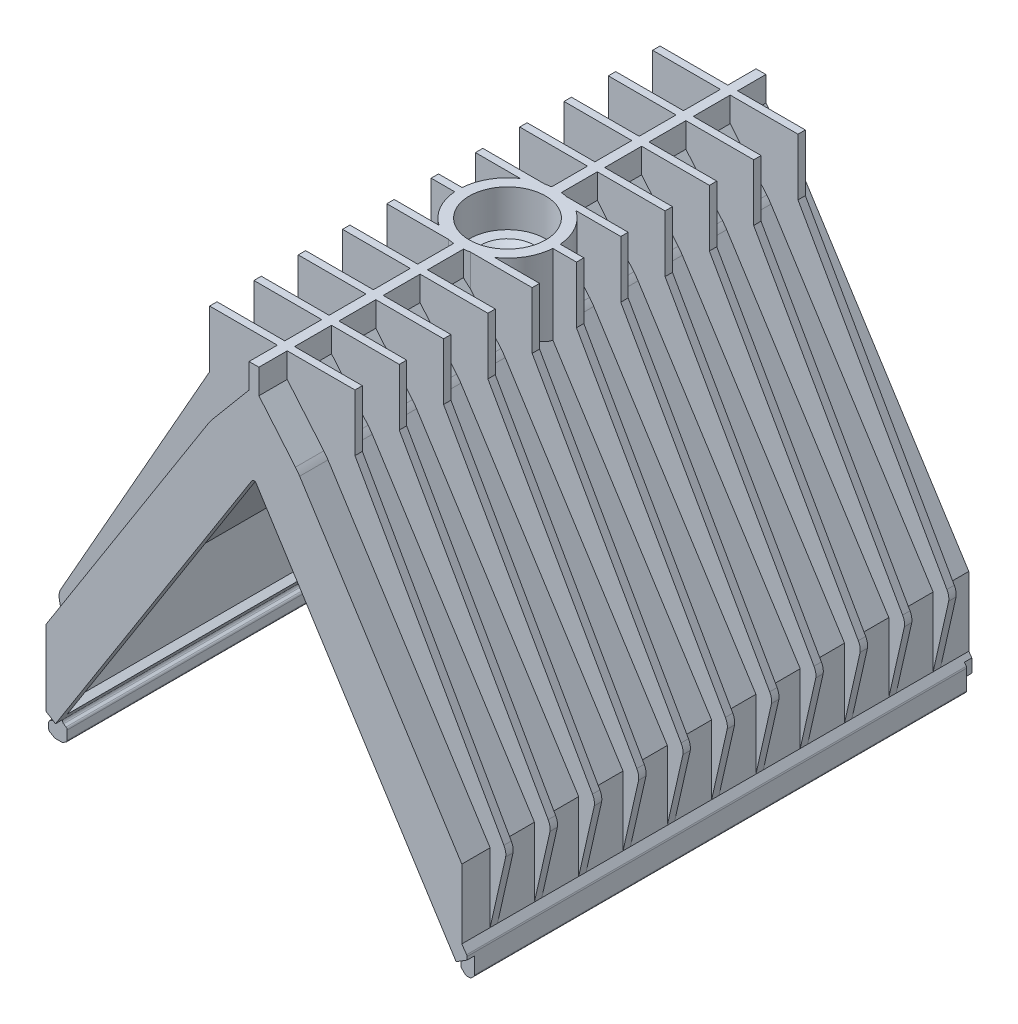
SolidWorks part; units mm, degrees
ref_plane "Front Plane" through (0, 0, 0) normal (0, 0, 1) x (1, 0, 0)
ref_plane "Top Plane" through (0, 0, 0) normal (0, 1, 0) x (1, 0, 0)
ref_plane "Right Plane" through (0, 0, 0) normal (1, 0, 0) x (0, 0, -1)
sketch "Sketch1" plane through (0, 0, 0) normal (0, 0, 1) x (1, 0, 0)
  line L0 (0, 0) -> (0, 124.0259) construction
  line L5 (-78.9086, 0) -> (78.9086, 0) construction
  line L9 (-0.8437, 122.6998) -> (-78.9086, 0) construction
  line L10 (0.8437, 122.6998) -> (81.0558, -3.3749) construction
  line L11 (81.0558, -3.3749) -> (83.5869, -1.7645) construction
  line L12 (83.5869, -1.7645) -> (3.3749, 124.3102) construction
  line L13 (-3.3749, 124.3102) -> (-81.4398, 1.6104) construction
  line L14 (-81.4398, 1.6104) -> (-78.9086, 0) construction
  line L15 (-81.4398, 1.6104) -> (-81.4398, 29.5541)
  line L16 (-81.4398, 29.5541) -> (-16.0306, 132.3621)
  line L17 (78.9086, 0) -> (81.4398, 1.6104) construction
  line L18 (81.4398, 1.6104) -> (81.4398, 29.5541)
  line L19 (81.4398, 29.5541) -> (16.0306, 132.3621)
  line L20 (-81.4398, 1.6104) -> (-78.9086, 0)
  line L23 (-84.4398, -4.2849) -> (-84.4398, 30.4275)
  line L24 (-84.4398, 30.4275) -> (-18.5617, 133.9725)
  line L25 (81.0558, -3.3749) -> (83.5869, -1.7645)
  line L26 (83.5869, -1.7645) -> (81.4398, 1.6104)
  line L29 (86.5869, -8.9852) -> (86.5869, -1.0301)
  line L30 (86.4044, -0.4541) -> (84.4398, 2.3339)
  line L31 (84.4398, 2.3339) -> (84.4398, 30.4275)
  line L32 (84.4398, 30.4275) -> (18.5617, 133.9725)
  line L33 (-106.5938, 164) -> (109.6618, 164) construction
  line L34 (0, 122.163) -> (0, 164) construction
  line L35 (0, 156.3889) -> (-16.853, 136.3043)
  line L36 (0, 156.3889) -> (16.853, 136.3043)
  line L37 (-78.9086, -5.5791) -> (-78.9086, -9.1985)
  line L38 (-81.1766, -10.9306) -> (-83.6407, -10.9306)
  line L39 (-78.9086, 0) -> (-80.65, -2.737)
  line L42 (-84.4398, -4.8622) -> (-84.4398, 3.8538) construction
  line L45 (-84.1407, -10.7966) -> (-85.9086, -9.7759)
  line L46 (-80.343, -4.1175) -> (-79.3718, -4.7354)
  line L49 (81.0558, -3.3749) -> (82.1294, -5.0623)
  line L50 (81.8225, -6.4428) -> (81.519, -6.6359)
  line L51 (81.0558, -7.4796) -> (81.0558, -8.5163)
  line L52 (81.3487, -9.2235) -> (82.7629, -10.6377)
  line L53 (83.47, -10.9306) -> (84.6416, -10.9306)
  line L54 (85.3487, -10.6377) -> (86.294, -9.6923)
  line L55 (-86.4086, -8.9098) -> (-86.4086, -6.5763)
  line L56 (-79.4086, -10.0645) -> (-80.6766, -10.7966)
  line L57 (-85.9086, -5.7102) -> (-84.9398, -5.1509)
  arc A0 (3.3749, 124.3102) -> (-3.3749, 124.3102) centre (0, 122.163) ccw construction
  arc A1 (0.8437, 122.6998) -> (-0.8437, 122.6998) centre (0, 122.163) ccw construction
  arc A2 (16.0306, 132.3621) -> (-16.0306, 132.3621) centre (0, 122.163) ccw
  arc A3 (-18.5617, 133.9725) -> (-16.853, 136.3043) centre (0, 122.163) cw
  arc A6 (16.853, 136.3043) -> (18.5617, 133.9725) centre (0, 122.163) cw
  arc A7 (-80.65, -2.737) -> (-80.343, -4.1175) centre (-79.8062, -3.2738) ccw
  arc A8 (-78.9086, -5.5791) -> (-79.3718, -4.7354) centre (-79.9086, -5.5791) ccw
  arc A9 (-79.4086, -10.0645) -> (-78.9086, -9.1985) centre (-79.9086, -9.1985) ccw
  arc A10 (-81.1766, -10.9306) -> (-80.6766, -10.7966) centre (-81.1766, -9.9306) ccw
  arc A11 (-83.6407, -10.9306) -> (-84.1407, -10.7966) centre (-83.6407, -9.9306) cw
  arc A12 (-85.9086, -9.7759) -> (-86.4086, -8.9098) centre (-85.4086, -8.9098) cw
  arc A13 (-85.9086, -5.7102) -> (-86.4086, -6.5763) centre (-85.4086, -6.5763) ccw
  arc A14 (-84.4398, -4.2849) -> (-84.9398, -5.1509) centre (-85.4398, -4.2849) cw
  arc A15 (86.5869, -1.0301) -> (86.4044, -0.4541) centre (85.5869, -1.0301) ccw
  arc A16 (86.294, -9.6923) -> (86.5869, -8.9852) centre (85.5869, -8.9852) ccw
  arc A17 (84.6416, -10.9306) -> (85.3487, -10.6377) centre (84.6416, -9.9306) ccw
  arc A18 (83.47, -10.9306) -> (82.7629, -10.6377) centre (83.47, -9.9306) cw
  arc A19 (81.3487, -9.2235) -> (81.0558, -8.5163) centre (82.0558, -8.5163) cw
  arc A20 (81.519, -6.6359) -> (81.0558, -7.4796) centre (82.0558, -7.4796) ccw
  arc A21 (81.8225, -6.4428) -> (82.1294, -5.0623) centre (81.2857, -5.5991) ccw
  point P30 (85.4221, 0.9399)
  point P67 (-80.9086, -10.9306)
  point P70 (-83.9086, -10.9306)
  point P85 (85.0558, -10.9306)
  point P88 (83.0558, -10.9306)
  point P91 (81.0558, -8.9306)
  point P94 (81.0558, -6.9306)
  point P97 (82.6662, -5.906)
  point P99 (-85.4242, -5.4306)
  point P100 (-79.8574, -4.4265)
  dimension "D4" = 151
  dimension "D5" = 160
  dimension "D6" = 4
  dimension "D7" = 1
  dimension "D10" = 19
  dimension "D18" = 120
  dimension "D29" = 1
  dimension "D30" = 1
  dimension "D32" = 1
  dimension "D1" = 3
  dimension "D2" = 3
  dimension "D3" = 147
  dimension "D8" = 15
  dimension "D9" = 15
  dimension "D11" = 3
  dimension "D12" = 3
  dimension "D13" = 135
  dimension "D14" = 3
  dimension "D15" = 3
  dimension "D16" = 3
  dimension "D17" = 3
  dimension "D19" = 140
  dimension "D20" = 120
  dimension "D21" = 3
  dimension "D22" = 2
  dimension "D23" = 135
  dimension "D24" = 2
  dimension "D25" = 2
  dimension "D26" = 3
  dimension "D27" = 2
  dimension "D28" = 150
  dimension "D31" = 7.5
  dimension "D33" = 5.5
  dimension "D34" = 6.5041
extrude "Boss-Extrude1" add sketch "Sketch1" along normal blind 100 and the other way blind 100
sketch3d "3DSketch3" plane through (0, 0, 0) normal (0, 0, 1) x (1, 0, 0)
  dimension "D1" = 175
sketch "Sketch2" plane through (0, 164.0694, 0) normal (0, -1, 0) x (-1, 0, 0)
  line L0 (16.0306, 100) -> (-16.0306, 100) construction
  line L1 (96, -1.5) -> (-96, -1.5)
  line L2 (96, -1.5) -> (96, 1.5)
  line L3 (96, 1.5) -> (-96, 1.5)
  line L4 (-96, -1.5) -> (-96, 1.5)
  line L5 (96, -1.5) -> (-96, 1.5) construction
  line L6 (96, 1.5) -> (-96, -1.5) construction
  line L7 (0, 0) -> (0, 114.6927) construction
  line L9 (0, 0) -> (96, 0) construction
  line L10 (-96, -19.5) -> (96, -19.5)
  line L11 (-96, -19.5) -> (-96, -16.5)
  line L12 (-96, -16.5) -> (96, -16.5)
  line L13 (96, -19.5) -> (96, -16.5)
  line L14 (-96, -19.5) -> (96, -16.5) construction
  line L15 (-96, -16.5) -> (96, -19.5) construction
  line L16 (-96, -37.5) -> (96, -37.5)
  line L17 (-96, -37.5) -> (-96, -34.5)
  line L18 (-96, -34.5) -> (96, -34.5)
  line L19 (96, -37.5) -> (96, -34.5)
  line L20 (-96, -37.5) -> (96, -34.5) construction
  line L21 (-96, -34.5) -> (96, -37.5) construction
  line L22 (-96, -55.5) -> (96, -55.5)
  line L23 (-96, -55.5) -> (-96, -52.5)
  line L24 (-96, -52.5) -> (96, -52.5)
  line L25 (96, -55.5) -> (96, -52.5)
  line L26 (-96, -55.5) -> (96, -52.5) construction
  line L27 (-96, -52.5) -> (96, -55.5) construction
  line L28 (-96, -73.5) -> (96, -73.5)
  line L29 (-96, -73.5) -> (-96, -70.5)
  line L30 (-96, -70.5) -> (96, -70.5)
  line L31 (96, -73.5) -> (96, -70.5)
  line L32 (-96, -73.5) -> (96, -70.5) construction
  line L33 (-96, -70.5) -> (96, -73.5) construction
  line L34 (-96, -91.5) -> (96, -91.5)
  line L35 (-96, -91.5) -> (-96, -88.5)
  line L36 (-96, -88.5) -> (96, -88.5)
  line L37 (96, -91.5) -> (96, -88.5)
  line L38 (-96, -91.5) -> (96, -88.5) construction
  line L39 (-96, -88.5) -> (96, -91.5) construction
  line L40 (-96, 88.5) -> (96, 91.5) construction
  line L41 (-96, 91.5) -> (96, 88.5) construction
  line L42 (-96, 70.5) -> (96, 73.5) construction
  line L43 (-96, 73.5) -> (96, 70.5) construction
  line L44 (-96, 52.5) -> (96, 55.5) construction
  line L45 (-96, 55.5) -> (96, 52.5) construction
  line L46 (-96, 34.5) -> (96, 37.5) construction
  line L47 (-96, 37.5) -> (96, 34.5) construction
  line L48 (-96, 16.5) -> (96, 19.5) construction
  line L49 (-96, 19.5) -> (96, 16.5) construction
  line L50 (96, 91.5) -> (96, 88.5)
  line L51 (-96, 88.5) -> (96, 88.5)
  line L52 (-96, 91.5) -> (-96, 88.5)
  line L53 (-96, 91.5) -> (96, 91.5)
  line L54 (96, 73.5) -> (96, 70.5)
  line L55 (-96, 70.5) -> (96, 70.5)
  line L56 (-96, 73.5) -> (-96, 70.5)
  line L57 (-96, 73.5) -> (96, 73.5)
  line L58 (96, 55.5) -> (96, 52.5)
  line L59 (-96, 52.5) -> (96, 52.5)
  line L60 (-96, 55.5) -> (-96, 52.5)
  line L61 (-96, 55.5) -> (96, 55.5)
  line L62 (96, 37.5) -> (96, 34.5)
  line L63 (-96, 34.5) -> (96, 34.5)
  line L64 (-96, 37.5) -> (-96, 34.5)
  line L65 (-96, 37.5) -> (96, 37.5)
  line L66 (96, 19.5) -> (96, 16.5)
  line L67 (-96, 16.5) -> (96, 16.5)
  line L68 (-96, 19.5) -> (-96, 16.5)
  line L69 (-96, 19.5) -> (96, 19.5)
  line L70 (-2, -100) -> (2, -100)
  line L71 (-2, -100) -> (-2, 100)
  line L72 (-2, 100) -> (2, 100)
  line L73 (2, -100) -> (2, 100)
  line L74 (-2, -100) -> (2, 100) construction
  line L75 (-2, 100) -> (2, -100) construction
  circle A0 centre (0, 0) radius 20
  point P0 (0, 0)
  point P10 (0, -18)
  point P15 (0, -36)
  point P20 (0, -54)
  point P25 (0, -72)
  point P30 (0, -90)
  point P56 (0, 90)
  point P57 (0, 72)
  point P58 (0, 54)
  point P59 (0, 36)
  point P60 (0, 18)
  dimension "D9" = 40
  dimension "D1" = 96
  dimension "D2" = 3
  dimension "D3" = 15
  dimension "D4" = 15
  dimension "D5" = 15
  dimension "D6" = 15
  dimension "D7" = 15
  dimension "D8" = 4
extrude "Boss-Extrude3" add sketch "Sketch2" along direction (0, -1, 0) on the side of the normal blind 175 contours L73 L51 L50 L53 | L51 L73 L53 L71 | L53 L73 L72 L71 | L51 L71 L53 L52 | L57 L73 L51 L71 | L55 L73 L57 L71 | L73 L55 L54 L57 | L55 L71 L57 L56 | L73 L59 L58 L61 | L65 L73 L59 L71 | L59 L71 L61 L60 | L59 L73 L61 L71 | L61 L73 L55 L71 | L73 L63 L62 L65 | L63 L73 L65 L71 | L63 L71 L65 L64 | A0 L73 L63 L71 | L69 A0 L67 L71 | L67 A0 L69 L73 | A0 L67 L66 L69 | L69 A0 L73 | L73 A0 L71 L69 | L71 A0 L69 | L67 A0 L3 L71 | L3 L73 L67 L71 | L3 A0 L67 L73 | L71 A0 L73 L10 | L73 A0 L10 | L1 A0 L12 L71 | L12 A0 L10 L71 | L10 A0 L71 | L10 L73 L12 L71 | L10 A0 L12 L73 | L12 A0 L1 L73 | L12 L73 L1 L71 | L1 A0 L3 L73 | L1 L73 L3 L71 | L3 A0 L1 L71 | A0 L3 L4 L1 | A0 L1 L2 L3 | A0 L69 L68 L67 | A0 L10 L13 L12 | A0 L12 L11 L10 | L73 L16 L19 L18 | L16 L71 L18 L17 | L73 L34 L37 L36 | L73 L28 L31 L30 | L73 L22 L25 L24 | L34 L71 L36 L35 | L70 L73 L34 L71 | L34 L73 L36 L71 | L36 L73 L28 L71 | L30 L73 L22 L71 | L28 L73 L30 L71 | L28 L71 L30 L29 | L22 L71 L24 L23 | L22 L73 L24 L71 | L24 L73 L16 L71 | L16 L73 L18 L71 | A0 L71 L18 L73 | L53 L50 L51 L52 | L73 L72 L71 L70 region at (-57.9906, 164.0694, 0) region at (-9.7744, 164.0694, 8.3272) region at (-10.9906, 164.0694, 0) region at (0, 164.0694, 9) region at (0, 164.0694, 0) region at (-5.5128, 164.0694, 17.7465) region at (-52.2103, 164.0694, 18.0187) region at (-9.7744, 164.0694, -8.3272) region at (9.7744, 164.0694, 8.3272) region at (10.9906, 164.0694, 0) region at (0, 164.0694, 18) region at (0, 164.0694, -9) region at (-2.8618, 164.0694, 19.6426) region at (-52.2103, 164.0694, -18.0187) region at (-5.5128, 164.0694, -17.7465) region at (57.9906, 164.0694, 0) region at (5.5128, 164.0694, 17.7465) region at (9.7744, 164.0694, -8.3272) region at (0, 164.0694, 19.7343) region at (0, 164.0694, 27.2333) region at (-2.8618, 164.0694, -19.6426) region at (52.2103, 164.0694, 18.0187) region at (2.8618, 164.0694, 19.6426) region at (5.5128, 164.0694, -17.7465) region at (0, 164.0694, -19.7343) region at (0, 164.0694, 36) region at (-49, 164.0694, 36) region at (0, 164.0694, -27.2333) region at (52.2103, 164.0694, -18.0187) region at (2.8618, 164.0694, -19.6426) region at (49, 164.0694, 36) region at (0, 164.0694, 45) region at (-49, 164.0694, -36) region at (0, 164.0694, -36) region at (0, 164.0694, 54) region at (-49, 164.0694, 54) region at (49, 164.0694, -36) region at (0, 164.0694, -45) region at (49, 164.0694, 54) region at (0, 164.0694, 63) region at (-49, 164.0694, -54) region at (0, 164.0694, -54) region at (0, 164.0694, 72) region at (-49, 164.0694, 72) region at (49, 164.0694, -54) region at (0, 164.0694, -63) region at (49, 164.0694, 72) region at (0, 164.0694, 81) region at (-49, 164.0694, -72) region at (0, 164.0694, -72) region at (0, 164.0694, 90) region at (-49, 164.0694, 90) region at (49, 164.0694, -72) region at (0, 164.0694, -81) region at (49, 164.0694, 90) region at (0, 164.0694, 95.75) region at (-49, 164.0694, -90) region at (0, 164.0694, -90) region at (49, 164.0694, -90) region at (0, 164.0694, -95.75)
sketch "Sketch4" plane through (0, 0, -91.5) normal (0, 0, -1) x (-1, 0, 0)
  line L1 (-81.0558, -3.3749) -> (-83.5869, -1.7645)
  line L2 (-83.5869, -1.7645) -> (-81.4398, 1.6104)
  line L3 (-81.4398, 1.6104) -> (-81.4398, 29.5541)
  line L4 (-81.4398, 29.5541) -> (-16.0306, 132.3621)
  line L5 (-81.4398, 29.5541) -> (-16.0306, 132.3621) construction
  line L6 (-16.0306, 132.3621) -> (-81.4398, 29.5541) construction
  line L8 (16.0306, 132.3621) -> (81.4398, 29.5541)
  line L9 (81.4398, 29.5541) -> (81.4398, 1.6104)
  line L10 (81.4398, 1.6104) -> (78.9086, 0)
  line L14 (-90.0461, 34.1063) -> (-29.53, 140.9508)
  line L15 (-81.4398, 29.5541) -> (-91.0411, 32.3495) construction
  line L16 (0, 122.163) -> (-29.53, 140.9508) construction
  line L17 (0, 122.163) -> (29.53, 140.9508) construction
  line L18 (84.4398, 1.6104) -> (90.5619, 30.1184)
  line L19 (89.9164, 34.3351) -> (29.53, 140.9508)
  line L20 (81.4398, 29.5541) -> (91.0411, 32.3495) construction
  line L22 (96, -10.9306) -> (96, 164.0694)
  line L24 (-96, 164.0694) -> (-96, -10.9306)
  line L26 (-86.5869, -8.9852) -> (-86.5869, -1.0301)
  line L27 (-29.53, 140.9508) -> (-29.53, 164.0694)
  line L28 (29.53, 164.0694) -> (96, 164.0694)
  line L29 (29.53, 164.0694) -> (29.53, 140.9508)
  line L30 (-29.53, 164.0694) -> (-96, 164.0694)
  line L31 (-81.0558, -3.3749) -> (-82.1294, -5.0623)
  line L32 (-81.0558, -7.4796) -> (-81.0558, -8.5163) construction
  line L33 (-81.8225, -6.4428) -> (-81.519, -6.6359)
  line L34 (-81.0558, -7.4796) -> (-81.0558, -8.5163)
  line L35 (-81.3487, -9.2235) -> (-82.7629, -10.6377)
  line L36 (-85.3487, -10.6377) -> (-86.294, -9.6923)
  line L37 (-84.6416, -10.9306) -> (-96, -10.9306)
  line L38 (-83.47, -10.9306) -> (81.1766, -10.9306)
  line L39 (84.9398, -5.1509) -> (85.9086, -5.7102)
  line L40 (86.4086, -6.5763) -> (86.4086, -8.9098)
  line L41 (85.9086, -9.7759) -> (84.1407, -10.7966)
  line L42 (78.9086, 0) -> (80.65, -2.737)
  line L43 (80.343, -4.1175) -> (79.3718, -4.7354)
  line L44 (78.9086, -9.1985) -> (78.9086, -5.5791)
  line L45 (79.4086, -10.0645) -> (80.6766, -10.7966)
  line L46 (84.4398, -4.2849) -> (84.4398, 30.4275) construction
  line L47 (96, -10.9306) -> (96, 164.0694) construction
  line L48 (84.4398, -4.2849) -> (84.4398, 1.6104)
  line L49 (96, -10.9306) -> (83.6407, -10.9306)
  line L50 (-86.4044, -0.4541) -> (-84.4398, 2.3339)
  line L51 (-84.4398, 2.3339) -> (-90.7716, 30.3486)
  line L52 (-96, -10.9306) -> (-96, 164.0694) construction
  line L53 (-96, 164.0694) -> (-2, 164.0694) construction
  arc A0 (-16.0306, 132.3621) -> (16.0306, 132.3621) centre (0, 122.163) cw
  arc A1 (-2, 141.0575) -> (-16.0306, 132.3621) centre (0, 122.163) ccw construction
  arc A3 (-90.0461, 34.1063) -> (-90.7716, 30.3486) centre (-84.8253, 31.1493) ccw
  arc A4 (90.5619, 30.1184) -> (89.9164, 34.3351) centre (84.6957, 31.3782) ccw
  arc A5 (-82.1294, -5.0623) -> (-81.8225, -6.4428) centre (-81.2857, -5.5991) ccw
  arc A6 (-82.1294, -5.0623) -> (-81.8225, -6.4428) centre (-81.2857, -5.5991) ccw construction
  arc A7 (-81.519, -6.6359) -> (-81.0558, -7.4796) centre (-82.0558, -7.4796) cw
  arc A8 (-86.5869, -1.0301) -> (-86.4044, -0.4541) centre (-85.5869, -1.0301) cw
  arc A9 (-81.0558, -8.5163) -> (-81.3487, -9.2235) centre (-82.0558, -8.5163) cw
  arc A10 (-81.3487, -9.2235) -> (-81.0558, -8.5163) centre (-82.0558, -8.5163) ccw construction
  arc A11 (-82.7629, -10.6377) -> (-83.47, -10.9306) centre (-83.47, -9.9306) cw
  arc A12 (-83.47, -10.9306) -> (-82.7629, -10.6377) centre (-83.47, -9.9306) ccw construction
  arc A13 (-84.6416, -10.9306) -> (-85.3487, -10.6377) centre (-84.6416, -9.9306) cw
  arc A14 (-85.3487, -10.6377) -> (-84.6416, -10.9306) centre (-84.6416, -9.9306) ccw construction
  arc A15 (-86.294, -9.6923) -> (-86.5869, -8.9852) centre (-85.5869, -8.9852) cw
  arc A16 (-86.5869, -8.9852) -> (-86.294, -9.6923) centre (-85.5869, -8.9852) ccw construction
  arc A17 (81.1766, -10.9306) -> (80.6766, -10.7966) centre (81.1766, -9.9306) cw
  arc A18 (-86.4044, -0.4541) -> (-86.5869, -1.0301) centre (-85.5869, -1.0301) ccw construction
  arc A19 (79.4086, -10.0645) -> (78.9086, -9.1985) centre (79.9086, -9.1985) cw
  arc A20 (78.9086, -9.1985) -> (79.4086, -10.0645) centre (79.9086, -9.1985) ccw construction
  arc A21 (78.9086, -5.5791) -> (79.3718, -4.7354) centre (79.9086, -5.5791) cw
  arc A22 (79.3718, -4.7354) -> (78.9086, -5.5791) centre (79.9086, -5.5791) ccw construction
  arc A23 (80.343, -4.1175) -> (80.65, -2.737) centre (79.8062, -3.2738) ccw
  arc A24 (80.343, -4.1175) -> (80.65, -2.737) centre (79.8062, -3.2738) ccw construction
  arc A25 (83.6407, -10.9306) -> (84.1407, -10.7966) centre (83.6407, -9.9306) ccw
  arc A26 (83.6407, -10.9306) -> (84.1407, -10.7966) centre (83.6407, -9.9306) ccw construction
  arc A27 (86.4086, -8.9098) -> (85.9086, -9.7759) centre (85.4086, -8.9098) cw
  arc A28 (85.9086, -9.7759) -> (86.4086, -8.9098) centre (85.4086, -8.9098) ccw construction
  arc A29 (85.9086, -5.7102) -> (86.4086, -6.5763) centre (85.4086, -6.5763) cw
  arc A30 (86.4086, -6.5763) -> (85.9086, -5.7102) centre (85.4086, -6.5763) ccw construction
  arc A31 (84.9398, -5.1509) -> (84.4398, -4.2849) centre (85.4398, -4.2849) cw
  arc A32 (84.4398, -4.2849) -> (84.9398, -5.1509) centre (85.4398, -4.2849) ccw construction
  arc A33 (80.6766, -10.7966) -> (81.1766, -10.9306) centre (81.1766, -9.9306) ccw construction
  dimension "D4" = 6
  dimension "D2" = 10
  dimension "D3" = 10
extrude "Cut-Extrude1" cut sketch "Sketch4" against normal through all and the other way blind 100 contours L26 A8 L50 L51 A3 L14 L27 L30 L24 L37 A13 L36 A15 | L45 A17 L38 A11 L35 A9 L34 A7 L33 A5 L31 L1 L2 L3 L4 A0 L8 L9 L10 L42 A23 L43 A21 L44 A19 | L49 A25 L41 A27 L40 A29 L39 A31 L48 L18 A4 L19 L29 L28 L22
sketch "Sketch5" plane through (0, 0, 100) normal (0, 0, 1) x (1, 0, 0)
  line L1 (-78.9086, 0) -> (-0.8437, 122.6998)
  line L2 (0.8437, 122.6998) -> (81.0558, -3.3749)
  line L3 (81.0558, -3.3749) -> (82.1294, -5.0623)
  line L7 (84.4398, 2.3339) -> (84.4398, 30.4275)
  line L8 (84.4398, 30.4275) -> (18.5617, 133.9725)
  line L10 (16.853, 136.3043) -> (2, 154.0054)
  line L11 (-2, 154.0054) -> (-16.853, 136.3043)
  line L14 (-18.5617, 133.9725) -> (-84.4398, 30.4275)
  line L15 (-84.4398, 30.4275) -> (-84.4398, 1.7012)
  line L17 (-2, 154.0054) -> (-2, 164.0694)
  line L18 (-2, 164.0694) -> (2, 164.0694)
  line L19 (2, 164.0694) -> (2, 154.0054)
  line L20 (-84.4398, -4.2849) -> (-84.4398, 30.4275) construction
  line L21 (-78.9086, 0) -> (-80.65, -2.737)
  line L22 (-80.65, -2.737) -> (-84.4398, -0.3258)
  line L23 (-84.4398, -0.3258) -> (-84.4398, 1.7012)
  line L24 (82.1294, -5.0623) -> (86.5869, -2.2849)
  line L25 (86.5869, -8.9852) -> (86.5869, -1.0301) construction
  line L26 (86.5869, -2.2849) -> (86.5869, -1.0301)
  line L27 (84.4398, 2.3339) -> (86.4044, -0.4541)
  arc A0 (86.4044, -0.4541) -> (86.5869, -1.0301) centre (85.5869, -1.0301) cw
  arc A2 (86.5869, -1.0301) -> (86.4044, -0.4541) centre (85.5869, -1.0301) ccw construction
  arc A3 (0.8437, 122.6998) -> (-0.8437, 122.6998) centre (0, 122.163) ccw
  arc A4 (16.853, 136.3043) -> (18.5617, 133.9725) centre (0, 122.163) cw
  arc A5 (-16.853, 136.3043) -> (-18.5617, 133.9725) centre (0, 122.163) ccw
  point P43 (0, 124.0259)
  dimension "D1" = 1
extrude "Boss-Extrude4" add sketch "Sketch5" along normal blind 3
sketch "Sketch6" plane through (0, 0, -100) normal (0, 0, -1) x (-1, 0, 0)
  line L0 (-81.947, -4.7756) -> (-81.0558, -3.3749)
  line L1 (-81.0558, -3.3749) -> (-0.8437, 122.6998)
  line L2 (0.8437, 122.6998) -> (78.9086, 0)
  line L5 (84.4398, -0.3258) -> (84.4398, 30.4275)
  line L6 (84.4398, 30.4275) -> (18.5617, 133.9725)
  line L8 (16.853, 136.3043) -> (2, 154.0054)
  line L9 (-2, 154.0054) -> (-16.853, 136.3043)
  line L11 (-18.5617, 133.9725) -> (-84.4398, 30.4275)
  line L12 (-84.4398, 30.4275) -> (-84.4398, 2.3339)
  line L13 (-84.4398, 2.3339) -> (-85.6713, 0.5862)
  line L14 (-85.6713, 0.5862) -> (-85.6713, -4.7756)
  line L15 (-85.6713, -4.7756) -> (-81.947, -4.7756)
  line L16 (-2, 154.0054) -> (-2, 164.0694)
  line L17 (-2, 164.0694) -> (2, 164.0694)
  line L18 (2, 164.0694) -> (2, 154.0054)
  line L19 (84.4398, -4.2849) -> (84.4398, 30.4275) construction
  line L20 (78.9086, 0) -> (80.65, -2.737)
  line L21 (80.65, -2.737) -> (84.4398, -0.3258)
  line L22 (-81.0558, -3.3749) -> (-82.1294, -5.0623) construction
  line L23 (-86.4044, -0.4541) -> (-84.4398, 2.3339) construction
  arc A0 (-16.853, 136.3043) -> (-18.5617, 133.9725) centre (0, 122.163) ccw
  arc A1 (16.853, 136.3043) -> (18.5617, 133.9725) centre (0, 122.163) cw
  arc A2 (-0.8437, 122.6998) -> (0.8437, 122.6998) centre (0, 122.163) cw
  point P43 (0, 124.0259)
  dimension "D1" = 1
extrude "Boss-Extrude5" add sketch "Sketch6" along normal blind 3
sketch "Sketch8" plane through (0, 0, 100) normal (0, 0, -1) x (-1, 0, 0)
  line L0 (-81.4398, 1.6104) -> (0, 129.6147)
  line L1 (0, 122.163) -> (0, 164) construction
  line L2 (0, 129.6147) -> (81.4398, 1.6104)
  line L3 (81.4398, 1.6104) -> (81.4398, 29.5541)
  line L4 (81.4398, 29.5541) -> (10.4312, 141.163)
  line L5 (10.4312, 141.163) -> (-10.4312, 141.163)
  line L6 (-10.4312, 141.163) -> (-81.4398, 29.5541)
  line L7 (-81.4398, 29.5541) -> (-81.4398, 1.6104)
  line L8 (3.3749, 124.3102) -> (81.4398, 1.6104) construction
  line L9 (-81.4398, 29.5541) -> (-16.0306, 132.3621) construction
  line L10 (81.4398, 29.5541) -> (16.0306, 132.3621) construction
  arc A0 (16.0306, 132.3621) -> (-16.0306, 132.3621) centre (0, 122.163) ccw construction
extrude "Boss-Extrude6" add sketch "Sketch8" along normal blind 2
sketch "Sketch9" plane through (0, 0, -100) normal (0, 0, 1) x (1, 0, 0)
  line L0 (-81.4398, 1.6104) -> (0, 129.6147)
  line L1 (0, 122.163) -> (0, 164) construction
  line L2 (0, 129.6147) -> (81.4398, 1.6104)
  line L3 (81.4398, 1.6104) -> (81.4398, 29.5541)
  line L4 (81.4398, 29.5541) -> (10.4312, 141.163)
  line L5 (10.4312, 141.163) -> (-10.4312, 141.163)
  line L6 (-10.4312, 141.163) -> (-81.4398, 29.5541)
  line L7 (-81.4398, 29.5541) -> (-81.4398, 1.6104)
  line L8 (83.5869, -1.7645) -> (3.3749, 124.3102) construction
  line L9 (81.4398, 29.5541) -> (16.0306, 132.3621) construction
  line L10 (-81.4398, 29.5541) -> (-16.0306, 132.3621) construction
  arc A0 (16.0306, 132.3621) -> (-16.0306, 132.3621) centre (0, 122.163) ccw construction
extrude "Boss-Extrude7" add sketch "Sketch9" along normal blind 1.5
sketch "Sketch10" plane through (0, 0, 0) normal (0, 0, 1) x (1, 0, 0)
  line L2 (-1.8895, 142.407) -> (-1, 141.1367)
  line L3 (-1, 141.1367) -> (0, 141.1367)
  line L5 (0, 141.1367) -> (0, 164.0694)
  line L6 (0, 164.0694) -> (-15.5, 164.0694)
  line L7 (-15.5, 164.0694) -> (-15.5, 149)
  line L8 (-15.5, 149) -> (-10.9898, 149)
  line L9 (-2.6262, 143.1437) -> (-10.9898, 149)
  line L13 (-2, 164.0694) -> (-29.53, 164.0694) construction
  line L14 (0, 122.163) -> (0, 164) construction
  arc A0 (16.0306, 132.3621) -> (-16.0306, 132.3621) centre (0, 122.163) ccw construction
  arc A1 (-1.8895, 142.407) -> (-2.6262, 143.1437) centre (-4.347, 140.6863) ccw
  dimension "D5" = 3
  dimension "D1" = 15.5
  dimension "D2" = 1
  dimension "D3" = 35
  dimension "D6" = 55
revolve "Cut-Revolve1" cut sketch "Sketch10" angle 360 about L5
